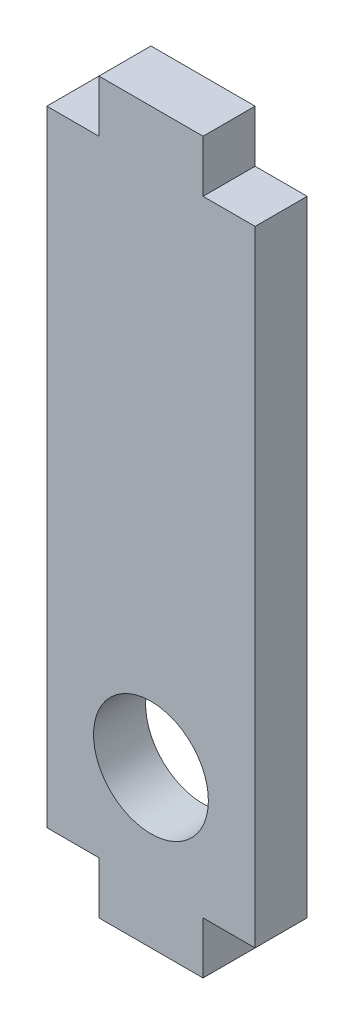
SolidWorks part; units mm, degrees
material "1060 Alloy"
ref_plane "Front Plane" through (0, 0, 0) normal (0, 0, 1) x (1, 0, 0)
ref_plane "Top Plane" through (0, 0, 0) normal (0, 1, 0) x (1, 0, 0)
ref_plane "Right Plane" through (0, 0, 0) normal (1, 0, 0) x (0, 0, -1)
sketch "Sketch1" plane through (0, 0, 0) normal (0, 0, 1) x (1, 0, 0)
  line L0 (55, 0) -> (-55, 0) construction
  line L1 (-12.7, -38.1) -> (12.7, -38.1)
  line L2 (-12.7, -38.1) -> (-12.7, 38.1)
  line L3 (-12.7, 38.1) -> (12.7, 38.1)
  line L4 (12.7, -38.1) -> (12.7, 38.1)
  line L5 (-12.7, -38.1) -> (12.7, 38.1) construction
  line L6 (-12.7, 38.1) -> (12.7, -38.1) construction
  line L7 (-12.7, 38.1) -> (12.7, 38.1)
  line L8 (-12.7, 38.1) -> (-12.7, 44.45)
  line L9 (-12.7, 44.45) -> (12.7, 44.45)
  line L10 (12.7, 38.1) -> (12.7, 44.45)
  line L11 (-12.7, -44.45) -> (12.7, -44.45)
  line L12 (12.7, -38.1) -> (12.7, -44.45)
  line L13 (-12.7, -38.1) -> (12.7, -38.1)
  line L14 (-12.7, -38.1) -> (-12.7, -44.45)
  line L15 (0, 44.45) -> (0, -44.45) construction
  line L16 (-6.35, -38.1) -> (6.35, -38.1)
  line L17 (-6.35, -38.1) -> (-6.35, -44.45)
  line L18 (-6.35, -44.45) -> (6.35, -44.45)
  line L19 (6.35, -38.1) -> (6.35, -44.45)
  line L21 (-6.35, 38.1) -> (6.35, 38.1)
  line L22 (-6.35, 38.1) -> (-6.35, 44.45)
  line L23 (-6.35, 44.45) -> (6.35, 44.45)
  line L24 (6.35, 38.1) -> (6.35, 44.45)
  point P0 (0, 0)
  point P10 (0, 44.45)
  point P11 (0, 38.1)
  point P18 (0, -38.1)
  point P19 (0, -44.45)
  point P30 (-6.35, 41.275)
  dimension "D1" = 25.4
  dimension "D2" = 76.2
  dimension "D3" = 25.4
  dimension "D4" = 6.35
  dimension "D5" = 12.7
  dimension "D6" = 12.7
extrude "Boss-Extrude1" add sketch "Sketch1" along normal blind 6.35 contours L1 L4 L3 L2 | L17 L16 L19 L18 | L22 L21 L24 L23 region at (0, 0, 0)
sketch "Sketch2" plane through (0, 0, 6.35) normal (0, 0, 1) x (1, 0, 0)
  line L8 (-12.7, -38.1) -> (-6.35, -38.1) construction
  circle A1 centre (0, -25.4) radius 7
  dimension "D2" = 12.7
  dimension "D1" = 14
extrude "Cut-Extrude1" cut sketch "Sketch2" against normal through all
